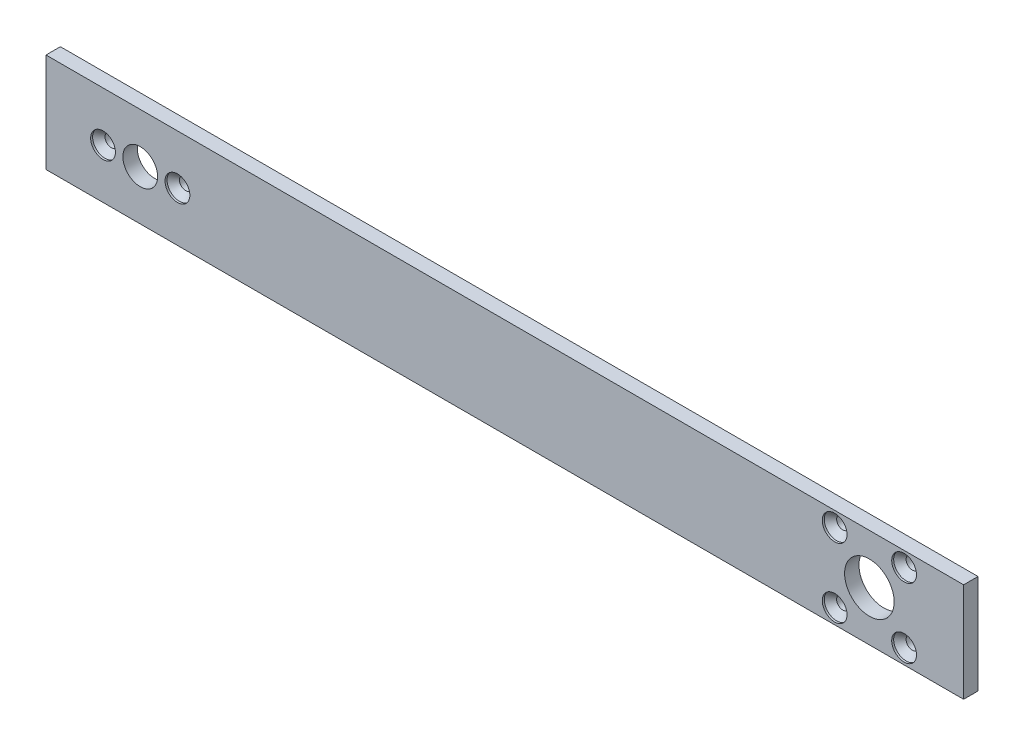
SolidWorks part; units mm, degrees
ref_plane "Front Plane" through (0, 0, 0) normal (0, 0, 1) x (1, 0, 0)
ref_plane "Top Plane" through (0, 0, 0) normal (0, 1, 0) x (1, 0, 0)
ref_plane "Right Plane" through (0, 0, 0) normal (1, 0, 0) x (0, 0, -1)
sketch "Sketch1" plane through (0, 0, 0) normal (0, 0, 1) x (1, 0, 0)
  line L1 (-92.5, 10) -> (92.5, 10)
  line L2 (-92.5, 10) -> (-92.5, -10)
  line L3 (-92.5, -10) -> (92.5, -10)
  line L4 (92.5, 10) -> (92.5, -10)
  line L5 (-92.5, 10) -> (92.5, -10) construction
  line L6 (-92.5, -10) -> (92.5, 10) construction
  point P0 (0, 0)
  dimension "D1" = 20
  dimension "D2" = 185
extrude "Base shape" add sketch "Sketch1" against normal blind 2.9
sketch "Sketch2" plane through (0, 0, 0) normal (0, 0, 1) x (1, 0, 0)
  line L0 (-83.5, 10) -> (-83.5, -10) construction
  line L1 (92.5, 10) -> (-92.5, 10) construction
  line L2 (-92.5, -10) -> (92.5, -10) construction
  line L3 (-92.5, 10) -> (-92.5, -10) construction
  line L4 (-92.5, 0) -> (92.5, 0) construction
  line L5 (92.5, -10) -> (92.5, 10) construction
  line L6 (-73.5, 10) -> (-73.5, -10) construction
  line L7 (0, 10) -> (0, -10) construction
  line L8 (73.5, 5) -> (92.5, 5) construction
  line L9 (-73.5, 3.5) -> (-92.5, 3.5) construction
  line L11 (80.5, -7) -> (66.5, -7)
  line L12 (80.5, -7) -> (80.5, 7)
  line L13 (80.5, 7) -> (66.5, 7)
  line L14 (66.5, -7) -> (66.5, 7)
  line L15 (80.5, -7) -> (66.5, 7) construction
  line L16 (80.5, 7) -> (66.5, -7) construction
  circle A0 centre (-73.5, 0) radius 10
  circle A1 centre (-81, 0) radius 1.25
  circle A2 centre (-66, 0) radius 1.25
  circle A3 centre (-73.5, 0) radius 3.5
  circle A4 centre (73.5, 0) radius 5
  circle A5 centre (66.5, 7) radius 1.25
  circle A6 centre (80.5, 7) radius 1.25
  circle A7 centre (80.5, -7) radius 1.25
  circle A8 centre (66.5, -7) radius 1.25
  dimension "D2" = 20
  dimension "D3" = 2.5
  dimension "D4" = 15
  dimension "D5" = 7
  dimension "D6" = 10
  dimension "D8" = 2.5
  dimension "D1" = 147
  dimension "D7" = 14
extrude "Motor cutouts" cut sketch "Sketch2" against normal up to next contours A5 | A6 | A7 | A8 | A1 | A2 | A3 | A4
hole_wizard "Countersunk chamfers" positions "Sketch3" profile "Sketch4" countersink size "M2.5" standard "ANSI Metric" end condition through all
sketch "Sketch3" plane through (0, 0, 0) normal (0, 0, 1) x (1, 0, 0)
  point P0 (-81, 0)
  point P3 (-66, 0)
  point P7 (66.5, 7)
  point P10 (80.5, 7)
  point P13 (66.5, -7)
  point P16 (80.5, -7)
sketch "Sketch4" plane through (-81, 0, 0) normal (1, 0, 0) x (0, -1, 0)
  line L0 (0, 0) -> (0, 2.9)
  line L1 (0, 2.9) -> (1.25, 2.9)
  line L2 (1.25, 2.9) -> (1.25, 1.65)
  line L3 (1.25, 1.65) -> (2.5, 0.4)
  line L4 (2.5, 0.4) -> (2.5, 0)
  line L6 (2.5, 0) -> (0, 0)
  line L7 (-1.25, 1.65) -> (-2.5, 0.4) construction
  line L11 (0, -6.35) -> (0, 107.95) construction
  dimension "Thru Hole Dia." = 2.5
  dimension "Thru Hole Depth" = 2.9
  dimension "C'Sink Dia." = 5
  dimension "C'Sink Angle" = 90
  dimension "Head Clearance" = 0.4
sketch "Sketch5" plane through (0, 0, -2.9) normal (0, 0, -1) x (-1, 0, 0)
  line L0 (0, 10) -> (0, -10) construction
  line L3 (-92.5, 10) -> (92.5, 10) construction
  line L4 (92.5, -10) -> (-92.5, -10) construction
  line L5 (-60, -7) -> (60, -7) construction
  line L6 (-60, -6) -> (60, -6)
  line L7 (-60, -8) -> (60, -8)
  arc A0 (-60, -6) -> (-60, -8) centre (-60, -7) ccw
  arc A1 (60, -8) -> (60, -6) centre (60, -7) ccw
  point P8 (0, -7)
  dimension "D1" = 120
  dimension "D2" = 2
  dimension "D3" = 2
extrude "PCB slot" cut sketch "Sketch5" against normal blind 1.5
